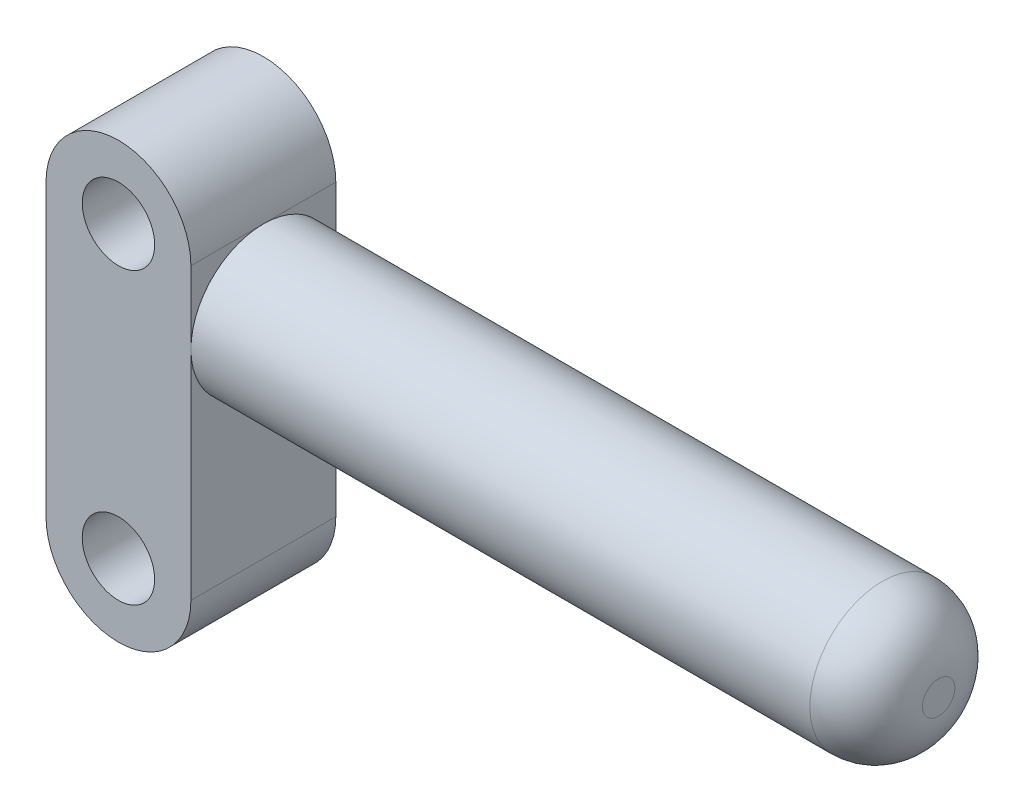
SolidWorks part; units mm, degrees
ref_plane "Plan de face" through (0, 0, 0) normal (0, 0, 1) x (1, 0, 0)
ref_plane "Plan de dessus" through (0, 0, 0) normal (0, 1, 0) x (1, 0, 0)
ref_plane "Plan de droite" through (0, 0, 0) normal (1, 0, 0) x (0, 0, -1)
other "Centre de masse"
sketch "Esquisse1" plane through (0, 0, 0) normal (0, 0, 1) x (1, 0, 0)
  line L0 (0, 10) -> (0, -10) construction
  line L1 (5, 10) -> (5, -10)
  line L2 (-5, 10) -> (-5, -10)
  line L3 (0, 0) -> (16.4339, 0) construction
  arc A0 (5, 10) -> (-5, 10) centre (0, 10) ccw
  arc A1 (-5, -10) -> (5, -10) centre (0, -10) ccw
  circle A2 centre (0, 10) radius 2.5
  circle A3 centre (0, -10) radius 2.5
  point P3 (0, 0)
  dimension "D3" = 5
  dimension "D2" = 10
extrude "Boss.-Extru.1" add sketch "Esquisse1" along normal mid plane 10
sketch "Esquisse2" plane through (5, 0, 0) normal (1, 0, 0) x (0, 0, -1)
  line L0 (0, 11.352) -> (0, 0) construction
  line L1 (0, 0) -> (4.254, 0) construction
  circle A0 centre (0, 5) radius 5
  dimension "D1" = 10
extrude "Boss.-Extru.2" add sketch "Esquisse2" along normal blind 46.6 contours A0
fillet "Congé1" radius 3.8833 1 edges at (51.6, 10, 0)
ref_axis "Axe1" through (0, 10, 5) along (0, 0, -1)
ref_point "Point1"
equation "\"e\"= 0.01m"
equation "\"d\"= 0.05"
equation "\"l\"= 0.01"
equation "\"D2@Esquisse1\"=\"l\""
equation "\"D1@Boss.-Extru.1\"=\"e\""
equation "\"Ddoigt\"= 0.01m"
equation "\"D1@Esquisse2\"=\"Ddoigt\""
equation "\"Ldoigt\"= 0.0466m"
equation "\"D1@Boss.-Extru.2\"=\"Ldoigt\""
equation "\"D1@Congé1\"=\"Ldoigt\"/12m"
